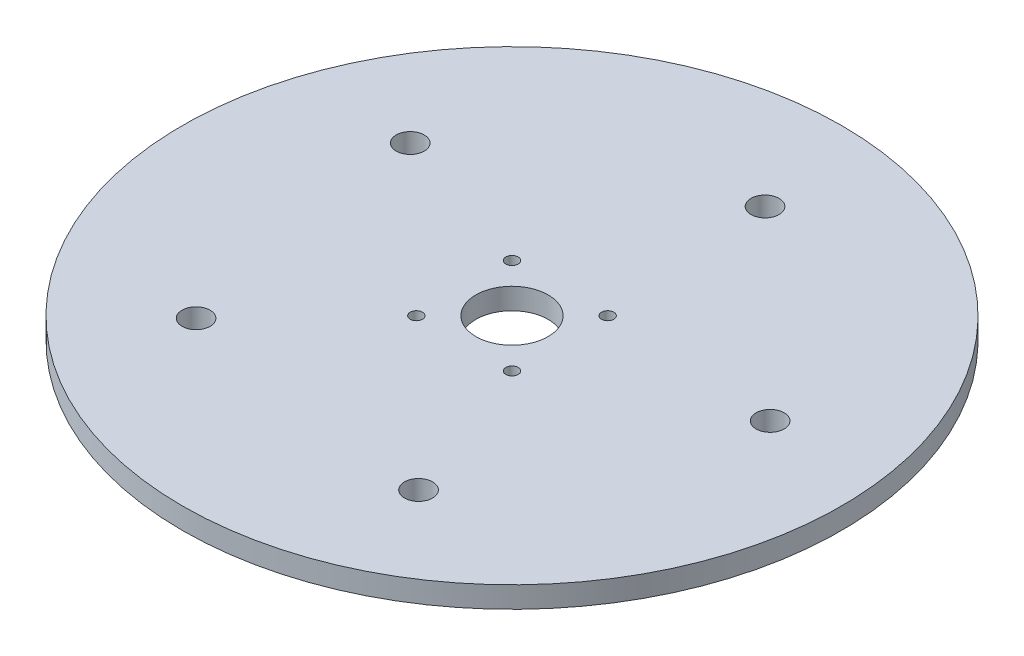
SolidWorks part; units mm, degrees
ref_plane "Front Plane" through (0, 0, 0) normal (0, 0, 1) x (1, 0, 0)
ref_plane "Top Plane" through (0, 0, 0) normal (0, 1, 0) x (1, 0, 0)
ref_plane "Right Plane" through (0, 0, 0) normal (1, 0, 0) x (0, 0, -1)
sketch "Sketch1" plane through (0, 0, 0) normal (0, 1, 0) x (1, 0, 0)
  circle A0 centre (0, 0) radius 77.5
  circle A1 centre (0, 0) radius 8.5
  dimension "D1" = 155
  dimension "D2" = 17
extrude "Body" add sketch "Sketch1" along normal blind 5
hole_wizard "M6 Clearance Hole1" positions "Sketch2" profile "Sketch3" hole size "M6" standard "ANSI Metric" end condition through all
sketch "Sketch2" plane through (0, 5, 0) normal (0, 1, 0) x (1, 0, 0)
  point P0 (7.5, 52)
  point P10 (51.7726, 8.936)
  point P11 (24.4972, -46.4773)
  point P12 (-36.6325, -37.6605)
  point P13 (-47.1373, 23.2018)
  point P15 (0, 0)
  dimension "D1" = 52
  dimension "D2" = 7.5
  dimension "D3" = 5
sketch "Sketch3" plane through (7.5, 5, -52) normal (1, 0, 0) x (0, 0, 1)
  line L0 (0, 0) -> (0, 5)
  line L1 (0, 5) -> (3.3, 5)
  line L2 (3.3, 5) -> (3.3, 0)
  line L5 (3.3, 0) -> (0, 0)
  line L11 (0, -6.35) -> (0, 107.95) construction
  dimension "Thru Hole Dia." = 6.6
  dimension "Thru Hole Depth" = 5
hole_wizard "M2.5 Clearance Hole1" positions "Sketch4" profile "Sketch5" hole size "M2.5" standard "ANSI Metric" end condition through all
sketch "Sketch4" plane through (0, 5, 0) normal (0, 1, 0) x (1, 0, 0)
  line L1 (11.25, -11.25) -> (-11.25, -11.25) construction
  line L2 (11.25, -11.25) -> (11.25, 11.25) construction
  line L3 (11.25, 11.25) -> (-11.25, 11.25) construction
  line L4 (-11.25, -11.25) -> (-11.25, 11.25) construction
  line L5 (11.25, -11.25) -> (-11.25, 11.25) construction
  line L6 (11.25, 11.25) -> (-11.25, -11.25) construction
  point P1 (0, 0)
  point P2 (-11.25, 11.25)
  point P21 (11.25, -11.25)
  point P22 (11.25, 11.25)
  point P23 (-11.25, -11.25)
  dimension "D1" = 22.5
sketch "Sketch5" plane through (0, 5, 0) normal (1, 0, 0) x (0, 0, 1)
  line L0 (0, 0) -> (0, 5)
  line L1 (0, 5) -> (1.45, 5)
  line L2 (1.45, 5) -> (1.45, 0)
  line L5 (1.45, 0) -> (0, 0)
  line L11 (0, -6.35) -> (0, 107.95) construction
  dimension "Thru Hole Dia." = 2.9
  dimension "Thru Hole Depth" = 5
